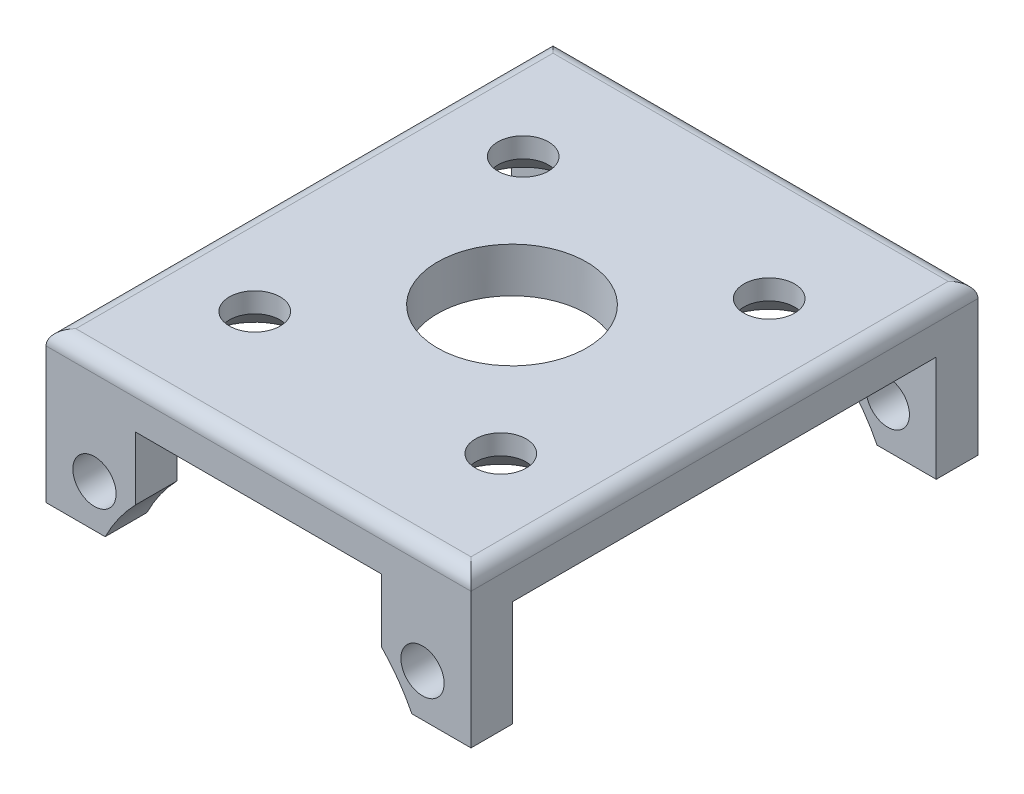
SolidWorks part; units mm, degrees
ref_plane "Front Plane" through (0, 0, 0) normal (0, 0, 1) x (1, 0, 0)
ref_plane "Top Plane" through (0, 0, 0) normal (0, 1, 0) x (1, 0, 0)
ref_plane "Right Plane" through (0, 0, 0) normal (1, 0, 0) x (0, 0, -1)
sketch "Sketch1" plane through (0, 0, 0) normal (0, 0, 1) x (1, 0, 0)
  line L0 (0, 0) -> (0, 5.0753) construction
  line L1 (-14.25, 11.25) -> (14.25, 11.25)
  line L2 (-14.25, 11.25) -> (-14.25, -35.25)
  line L3 (-14.25, -35.25) -> (14.25, -35.25)
  line L4 (14.25, 11.25) -> (14.25, -35.25)
  line L5 (-14.25, 11.25) -> (-7.75, 11.25)
  line L6 (-14.25, 11.25) -> (-14.25, 4.75)
  line L7 (-14.25, 4.75) -> (-7.75, 4.75)
  line L8 (-7.75, 11.25) -> (-7.75, 4.75)
  line L9 (0, 0) -> (3.7441, 0) construction
  line L10 (14.25, 4.75) -> (7.75, 4.75)
  line L11 (7.75, 11.25) -> (7.75, 4.75)
  line L12 (-14.25, -12) -> (23.601, -12) construction
  line L13 (7.75, -35.25) -> (7.75, -29.75)
  line L14 (14.25, -28.75) -> (8.75, -28.75)
  line L15 (-7.75, -35.25) -> (-7.75, -29.75)
  line L16 (-14.25, -28.75) -> (-8.75, -28.75)
  line L18 (14.25, 11.25) -> (-14.25, 11.25)
  line L19 (14.25, 11.25) -> (14.25, 15.25)
  line L20 (14.25, 15.25) -> (-14.25, 15.25)
  line L21 (-14.25, 11.25) -> (-14.25, 15.25)
  line L22 (-14.25, 4.75) -> (-16.25, 4.75)
  line L23 (-14.25, 4.75) -> (-14.25, 15.25)
  line L24 (-14.25, 15.25) -> (-16.25, 15.25)
  line L25 (-16.25, 4.75) -> (-16.25, 15.25)
  line L26 (14.25, 15.25) -> (16.25, 15.25)
  line L27 (14.25, 15.25) -> (14.25, 4.75)
  line L28 (14.25, 4.75) -> (16.25, 4.75)
  line L29 (16.25, 15.25) -> (16.25, 4.75)
  line L30 (-8.25, 11.25) -> (8.25, 11.25)
  line L31 (-8.25, 11.25) -> (-8.25, 4.75)
  line L32 (-8.25, 4.75) -> (8.25, 4.75)
  line L33 (8.25, 11.25) -> (8.25, 4.75)
  line L34 (-8.25, 11.25) -> (8.25, 11.25)
  line L35 (-8.25, 11.25) -> (-8.25, 12.25)
  line L36 (-8.25, 12.25) -> (8.25, 12.25)
  line L37 (8.25, 11.25) -> (8.25, 12.25)
  circle A1 centre (0, 0) radius 10.45
  circle A2 centre (-11, 8) radius 1.45
  circle A3 centre (11, 8) radius 1.45
  circle A4 centre (11, -32) radius 1.45
  circle A5 centre (-11, -32) radius 1.45
  arc A7 (-7.75, -29.75) -> (-8.75, -28.75) centre (-8.75, -29.75) ccw
  arc A8 (8.75, -28.75) -> (7.75, -29.75) centre (8.75, -29.75) ccw
  circle A9 centre (0, 0) radius 11.5
  point P0 (0, 0)
  point P35 (-7.75, -28.75)
  point P38 (7.75, -28.75)
  dimension "D1" = 28.5
  dimension "D2" = 46.5
  dimension "D3" = 23
  dimension "D4" = 11.25
  dimension "D5" = 2.9
  dimension "D6" = 3.25
  dimension "D7" = 3.25
  dimension "D10" = 3.25
  dimension "D12" = 1
  dimension "D16" = 20.9
  dimension "D17" = 0.5
  dimension "D11" = 3.25
  dimension "D13" = 4
  dimension "D14" = 2
  dimension "D15" = 2
  dimension "D18" = 0.5
  dimension "D19" = 1
  dimension "D8" = 2
  dimension "D9" = 2
extrude "Boss-Extrude7" add sketch "Sketch1" along normal blind 17 and the other way blind 17 contours L37 L18 L19 L20 L21 L1 L35 L36 | A9 L10 L4 L18 L33 A3 | A9 L31 L1 L2 L7 A2 region at (0, 13.5038, 0) region at (-11.25, 11.1615, 0) region at (14.1615, 8, 0)
sketch "Sketch34" plane through (-14.25, 0, 0) normal (-1, 0, 0) x (0, 0, 1)
  line L0 (-17, 4.75) -> (17, 4.75) construction
  line L1 (-14.2, 12.25) -> (14.2, 12.25)
  line L2 (-14.2, 12.25) -> (-14.2, 4.75)
  line L3 (-14.2, 4.75) -> (14.2, 4.75)
  line L4 (14.2, 12.25) -> (14.2, 4.75)
  line L5 (-17, 4.75) -> (-17, 15.25) construction
  line L6 (17, 4.75) -> (17, 15.25) construction
  line L7 (-17, 15.25) -> (17, 15.25) construction
  dimension "D1" = 2.8
  dimension "D2" = 2.8
  dimension "D3" = 3
extrude "Cut-Extrude11" cut sketch "Sketch34" against normal through all
sketch "Sketch35" plane through (0, 15.25, 0) normal (0, 1, 0) x (1, 0, 0)
  circle A0 centre (0, 0) radius 5
extrude "Cut-Extrude12" cut sketch "Sketch35" against normal through all
sketch "Sketch39" plane through (0, 12.25, 0) normal (0, -1, 0) x (1, 0, 0)
  line L0 (-14.25, 14.2) -> (-14.25, -14.2) construction
  line L1 (-8.25, 17) -> (8.25, 17) construction
  line L3 (0, 0) -> (0, 7.1623) construction
  line L4 (0, 0) -> (6.1391, 0) construction
  circle A0 centre (-8.25, 9) radius 1.5
  circle A1 centre (8.25, 9) radius 1.5
  circle A2 centre (-8.25, -9) radius 1.5
  circle A3 centre (8.25, -9) radius 1.5
  point P0 (-8.25, 9)
  point P9 (8.25, 9)
  point P12 (-8.25, -9)
  point P14 (8.25, -9)
  dimension "D1" = 6
  dimension "D2" = 8
hole_wizard "CSK for M3 Hex Socket Countersunk Cap Screw3" positions "Sketch39" profile "Sketch40" countersink size "M3" standard "ISO" end condition through all
sketch "Sketch40" plane through (-8.25, 12.25, 9) normal (1, 0, 0) x (0, 0, -1)
  line L0 (0, 0) -> (0, 3)
  line L1 (0, 3) -> (1.7, 3)
  line L2 (1.7, 3) -> (1.7, 1.66)
  line L3 (1.7, 1.66) -> (3.36, 0)
  line L5 (3.36, 0) -> (0, 0)
  line L6 (-1.7, 1.66) -> (-3.36, 0) construction
  line L11 (0, -6.35) -> (0, 107.95) construction
  dimension "Thru Hole Dia." = 3.4
  dimension "Thru Hole Depth" = 3
  dimension "Near C'Sink Dia." = 6.72
  dimension "Near C'Sink Angle" = 90
fillet "Fillet5" radius 1 4 edges at (14.25, 15.25, 0) (-14.25, 15.25, 0) (0, 15.25, -17) (0, 15.25, 17)
sketch "Sketch41" plane through (0, 0, 17) normal (0, 0, 1) x (1, 0, 0)
  line L0 (14.25, 4.75) -> (14.25, 14.25) construction
  line L1 (-14.25, 4.75) -> (14.25, 4.75)
  line L2 (-14.25, 4.75) -> (-14.25, 5.15)
  line L3 (-14.25, 5.15) -> (14.25, 5.15)
  line L4 (14.25, 4.75) -> (14.25, 5.15)
  dimension "D1" = 0.4
extrude "Cut-Extrude13" cut sketch "Sketch41" against normal through all
sketch "Sketch45" plane through (0, 0, 17) normal (0, 0, 1) x (1, 0, 0)
  circle A0 centre (11, 8) radius 1.45
  circle A1 centre (0, 0) radius 11.5
